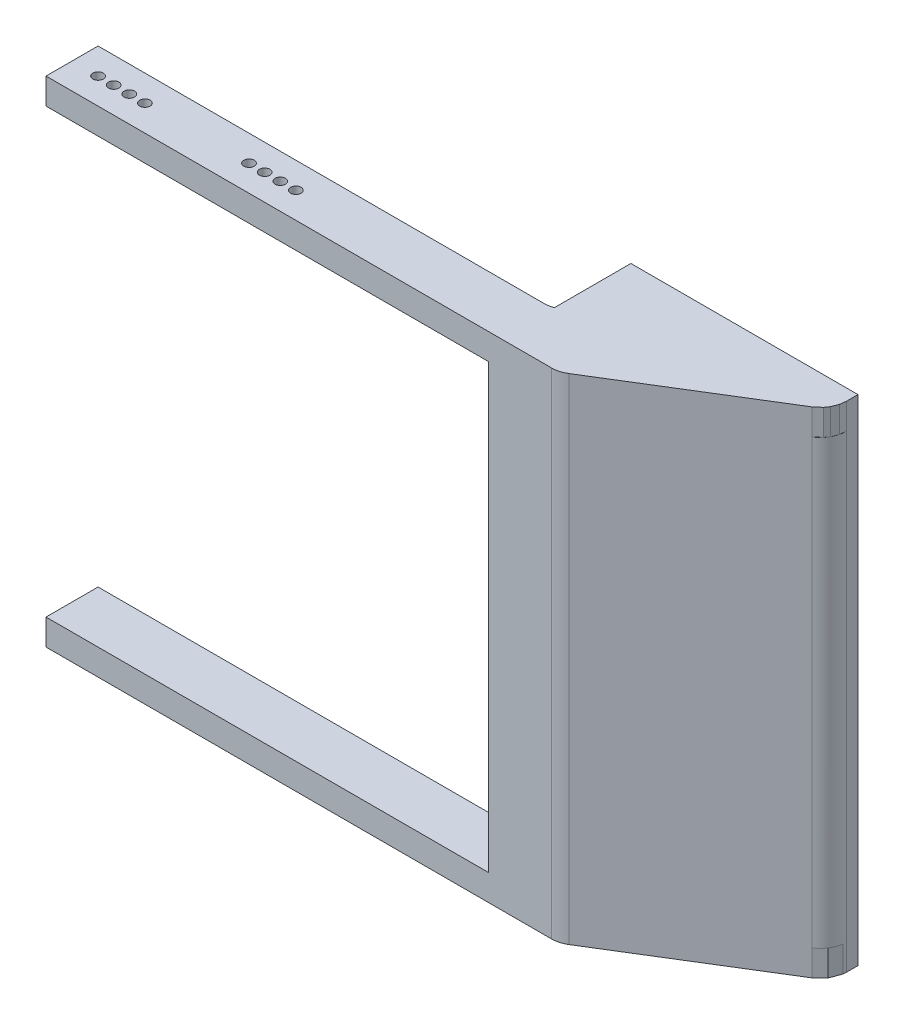
SolidWorks part; units mm, degrees
other "Marquage1"
sketch "Esquisse6" plane through (-75, 0, -38.2843) normal (-0.024, -0.0063, -0.9997) x (-0.9942, -0.1051, 0.0245)
ref_plane "Front Plane" through (0, 0, 0) normal (0, 0, 1) x (1, 0, 0)
ref_plane "Top Plane" through (0, 0, 0) normal (0, 1, 0) x (1, 0, 0)
ref_plane "Right Plane" through (0, 0, 0) normal (1, 0, 0) x (0, 0, -1)
sketch "Sketch1" plane through (0, 0, 0) normal (0, 1, 0) x (1, 0, 0)
  line L0 (-52.25, 0) -> (52.25, 0) construction
  line L1 (30, 0) -> (-75, 0)
  line L4 (-75, 0) -> (-75, 10)
  line L5 (30, 10) -> (55.9808, 25)
  line L6 (55.9808, 25) -> (55.9808, 20)
  line L7 (55.9808, 20) -> (28.4498, 3.0365)
  line L8 (30, 10) -> (12.5, 25)
  line L9 (12.5, 25) -> (12.5, 20)
  line L10 (12.5, 20) -> (24.1667, 10)
  line L11 (28.4498, 3.0365) -> (23.5217, 0)
  line L12 (-75, 10) -> (24.1667, 10)
  line L13 (23.5217, 0) -> (-75, 0)
  line L14 (24.1667, 10) -> (30, 10)
  dimension "D10" = 10
  dimension "D1" = 30
  dimension "D2" = 30
  dimension "D3" = 75
  dimension "D4" = 10
  dimension "D5" = 20
  dimension "D6" = 30
  dimension "D7" = 5
  dimension "D8" = 20
  dimension "D9" = 5
  dimension "D11" = 109.399
extrude "Boss-Extrude3" add sketch "Sketch1" along normal blind 95 contours L4 L12 L10 L9 L8 L5 L6 L7 L11 L13
fillet "Fillet8" radius 5 1 edges at (24.1667, 47.5, -10)
fillet "Fillet9" radius 5 2 edges at (55.9808, 47.5, -20) (12.5, 47.5, -20)
fillet "Fillet10" radius 5 1 edges at (23.5217, 47.5, 0)
sketch "Esquisse3" plane through (0, 0, -10) normal (0, 0, -1) x (-1, 0, 0)
  line L0 (75, 95) -> (75, 0) construction
  line L1 (75, 5) -> (45, 5)
  line L2 (75, 5) -> (75, 90)
  line L3 (75, 90) -> (45, 90)
  line L4 (45, 5) -> (45, 90)
  line L5 (75, 0) -> (-10.6504, 0) construction
  line L6 (75, 95) -> (-10.6504, 95) construction
  dimension "D1" = 5
  dimension "D2" = 5
  dimension "D3" = 30
extrude "Enlèv. mat.-Extru.1" cut sketch "Esquisse3" against normal through all contours L2 L1 L4 L3
sketch "Esquisse5" plane through (0, 0, -10) normal (0, 0, -1) x (-1, 0, 0)
  line L1 (45, 5) -> (35, 5)
  line L2 (45, 5) -> (45, 65)
  line L3 (45, 65) -> (35, 65)
  line L4 (35, 5) -> (35, 65)
  dimension "D1" = 10
extrude "Enlèv. mat.-Extru.2" cut sketch "Esquisse5" against normal through all contours L2 L1 L4 L3
sketch "Esquisse14" plane through (0, 0, -10) normal (0, 0, -1) x (-1, 0, 0)
  line L0 (45, 65) -> (35, 65) construction
  line L1 (45, 90) -> (35, 90)
  line L2 (45, 90) -> (45, 65)
  line L3 (45, 65) -> (35, 65)
  line L4 (35, 90) -> (35, 65)
extrude "Enlèv. mat.-Extru.7" cut sketch "Esquisse14" against normal through all
sketch "Esquisse15" plane through (0, 0, -10) normal (0, 0, -1) x (-1, 0, 0)
  line L1 (35, 90) -> (5, 90)
  line L2 (35, 90) -> (35, 5)
  line L3 (35, 5) -> (5, 5)
  line L4 (5, 90) -> (5, 5)
  dimension "D1" = 30
extrude "Enlèv. mat.-Extru.8" cut sketch "Esquisse15" against normal through all
sketch "Esquisse21" plane through (0, 0, -10) normal (0, 0, -1) x (-1, 0, 0)
  line L1 (5, 90) -> (-10, 90)
  line L2 (5, 90) -> (5, 5)
  line L3 (5, 5) -> (-10, 5)
  line L4 (-10, 90) -> (-10, 5)
  dimension "D1" = 15
extrude "Enlèv. mat.-Extru.9" cut sketch "Esquisse21" against normal through all
sketch "Esquisse61" plane through (0, 0, 0) normal (0, 1, 0) x (1, 0, 0)
  line L1 (12.2705, 25) -> (55.9406, 25)
  line L2 (12.2705, 25) -> (12.2705, 4.0617)
  line L3 (12.2705, 4.0617) -> (55.9406, 4.0617)
  line L4 (55.9406, 25) -> (55.9406, 4.0617)
extrude "Boss.-Extru.3" add sketch "Esquisse61" along normal blind 5
sketch "Esquisse63" plane through (0, 5, 0) normal (0, 1, 0) x (1, 0, 0)
  line L0 (55.9406, 22.16) -> (55.183, 20.0827)
  line L1 (55.183, 20.0827) -> (53.6036, 18.5353)
  line L2 (53.6036, 18.5353) -> (30.1137, 4.0617)
  line L3 (30.1137, 4.0617) -> (55.9406, 4.0617)
  line L4 (55.9406, 4.0617) -> (55.9406, 22.16)
  arc A0 (53.6036, 18.5353) -> (55.9406, 22.16) centre (50.9808, 22.7921) ccw construction
extrude "Enlèv. mat.-Extru.18" cut sketch "Esquisse63" against normal blind 5
sketch "Esquisse69" plane through (0, 95, 0) normal (0, 1, 0) x (1, 0, 0)
  line L1 (55.9808, 25) -> (12.3569, 25)
  line L2 (55.9808, 25) -> (55.9808, 7.8571)
  line L3 (55.9808, 7.8571) -> (12.3569, 7.8571)
  line L4 (12.3569, 25) -> (12.3569, 7.8571)
extrude "Boss.-Extru.4" add sketch "Esquisse69" against normal blind 5
sketch "Esquisse71" plane through (0, 90, 0) normal (0, -1, 0) x (1, 0, 0)
  line L0 (55.9808, -22.7921) -> (55.8261, -21.5582)
  line L1 (55.8261, -21.5582) -> (55.3462, -20.3543)
  line L2 (55.3462, -20.3543) -> (54.8122, -19.5797)
  line L3 (54.8122, -19.5797) -> (53.6036, -18.5353)
  line L4 (53.6036, -18.5353) -> (36.2734, -7.8571)
  line L5 (36.2734, -7.8571) -> (55.9808, -7.8571)
  line L6 (55.9808, -7.8571) -> (55.9808, -22.7921)
  arc A0 (55.9808, -22.7921) -> (53.6036, -18.5353) centre (50.9808, -22.7921) ccw construction
extrude "Enlèv. mat.-Extru.21" cut sketch "Esquisse71" against normal blind 10
sketch "Esquisse77" plane through (3.1699, 0, 5.4904) normal (-0.5, 0, -0.866) x (-0.866, 0, 0.5)
  line L0 (-30.9808, 90) -> (-40.9808, 90)
  line L1 (-60.9808, 90) -> (-30.9808, 90) construction
  line L2 (-40.9808, 90) -> (-31.4808, 5)
  line L3 (-30.9808, 5) -> (-60.9344, 5) construction
  line L4 (-31.4808, 5) -> (-30.9808, 5)
  line L5 (-30.9808, 90) -> (-30.9808, 5) construction
  line L6 (-30.9808, 5) -> (-30.9808, 90)
  dimension "D1" = 0.5
  dimension "D2" = 10
extrude "Boss.-Extru.7" add sketch "Esquisse77" along normal blind 17
sketch "Esquisse79" plane through (0, 90, 0) normal (0, 1, 0) x (1, 0, 0)
  line L0 (21.9808, 25) -> (32.8868, 25)
  line L1 (32.8868, 25) -> (30.1603, 29.7224)
  line L2 (30.1603, 29.7224) -> (21.9808, 25)
extrude "Enlèv. mat.-Extru.25" cut sketch "Esquisse79" against normal up to next and the other way through all
sketch "Esquisse80" plane through (0, 5, 0) normal (0, 1, 0) x (1, 0, 0)
  line L3 (12.5, 25) -> (30, 10)
  line L4 (30, 10) -> (21.25, 25)
  line L5 (55.9406, 25) -> (12.5, 25) construction
  line L6 (21.25, 25) -> (12.5, 25)
extrude "Boss.-Extru.10" add sketch "Esquisse80" along normal blind 86
sketch "Esquisse84" plane through (0, 90, 0) normal (0, -1, 0) x (-1, 0, 0)
  line L0 (75, 0) -> (75, 10) construction
  line L1 (75, 0) -> (-10, 0) construction
  circle A0 centre (70, 5) radius 1
  circle A1 centre (67, 5) radius 1
  circle A2 centre (64, 5) radius 1
  circle A3 centre (61, 5) radius 1
  circle A4 centre (41, 5) radius 1
  circle A5 centre (38, 5) radius 1
  circle A6 centre (35, 5) radius 1
  circle A7 centre (32, 5) radius 1
  point P2 (0, 0)
  point P9 (64.9797, 5.2074)
  point P12 (61.0873, 5.5627)
  point P15 (56.671, 5)
  point P16 (65.4222, 5)
  point P17 (61.0989, 5)
  point P18 (57.5795, 5.2082)
  point P19 (57.4514, 5)
  point P22 (53.8983, 5)
  point P25 (36.9375, 5)
  point P28 (33.3745, 5)
  point P31 (28.0604, 5)
  dimension "D2" = 2
  dimension "D1" = 5
  dimension "D3" = 5
  dimension "D4" = 3
  dimension "D5" = 3
  dimension "D6" = 3
  dimension "D7" = 20
  dimension "D8" = 3
  dimension "D9" = 3
  dimension "D10" = 3
extrude "Enlèv. mat.-Extru.26" cut sketch "Esquisse84" against normal through all
